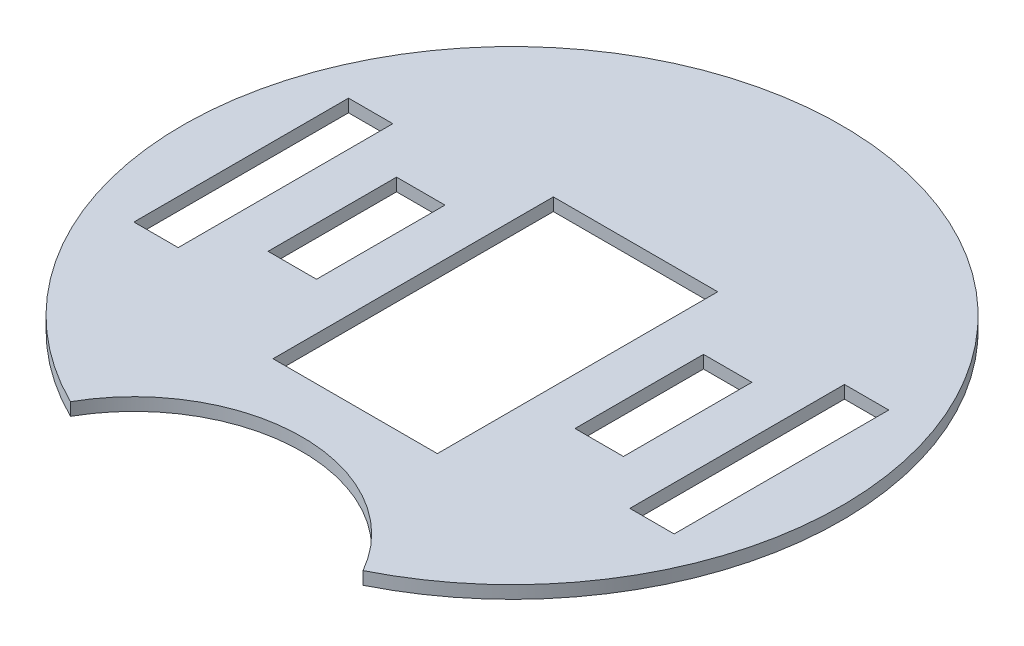
SolidWorks part; units mm, degrees
ref_plane "Front Plane" through (0, 0, 0) normal (0, 0, 1) x (1, 0, 0)
ref_plane "Top Plane" through (0, 0, 0) normal (0, 1, 0) x (1, 0, 0)
ref_plane "Right Plane" through (0, 0, 0) normal (1, 0, 0) x (0, 0, -1)
sketch "Sketch1" plane through (0, 0, 0) normal (0, 1, 0) x (1, 0, 0)
  line L0 (0, -86.0416) -> (-33.2911, -67.2064) construction
  line L1 (0, -86.0416) -> (0, 0) construction
  arc A0 (33.2911, -67.2064) -> (-33.2911, -67.2064) centre (0, 0) ccw
  arc A1 (33.2911, -67.2064) -> (-33.2911, -67.2064) centre (0, -86.0416) ccw
  dimension "D1" = 150
  dimension "D2" = 76.5
  dimension "D3" = 60.5
extrude "Boss-Extrude1" add sketch "Sketch1" along normal blind 2.9
sketch "solenoid placement" plane through (0, 2.9, 0) normal (0, 1, 0) x (1, 0, 0)
  line L4 (-18.7, -35.7) -> (18.7, -35.7)
  line L5 (18.7, -35.7) -> (18.7, 28.1)
  line L6 (18.7, 28.1) -> (-18.7, 28.1)
  line L7 (-18.7, 28.1) -> (-18.7, -35.7)
  line L8 (-18.7, -35.7) -> (18.7, -35.7)
  line L9 (18.7, -35.7) -> (18.7, 28.1)
  line L10 (18.7, 28.1) -> (-18.7, 28.1)
  line L11 (-18.7, 28.1) -> (-18.7, -35.7)
  circle A1 centre (0, 0) radius 75 construction
  arc A2 (33.2911, -67.2064) -> (-33.2911, -67.2064) centre (0, 0) ccw construction
  dimension "D1" = 0
extrude "Cut-Extrude1" cut sketch "solenoid placement" against normal through all
sketch "Sketch2" plane through (0, 2.9, 0) normal (0, 1, 0) x (1, 0, 0)
  line L0 (51.6937, -24.2881) -> (51.6937, 23.9564) construction
  line L1 (-61.1724, -24.2881) -> (-51.6937, -24.2881) construction
  line L2 (-61.1724, -24.2881) -> (-61.1724, 23.9564) construction
  line L3 (-61.1724, 23.9564) -> (-51.6937, 23.9564) construction
  line L4 (-51.6937, -24.2881) -> (-51.6937, 23.9564) construction
  line L5 (61.1724, 23.9564) -> (51.6937, 23.9564) construction
  line L6 (61.1724, -24.2881) -> (61.1724, 23.9564) construction
  line L7 (61.1724, -24.2881) -> (51.6937, -24.2881) construction
  line L8 (61.4724, -24.5881) -> (61.4724, 24.2564)
  line L9 (61.4724, -24.5881) -> (51.3937, -24.5881)
  line L10 (51.3937, -24.5881) -> (51.3937, 24.2564)
  line L11 (61.4724, 24.2564) -> (51.3937, 24.2564)
  line L12 (0, 0) -> (0, 75) construction
  line L13 (-61.4724, 24.2564) -> (-51.3937, 24.2564)
  line L14 (-51.3937, -24.5881) -> (-51.3937, 24.2564)
  line L15 (-61.4724, -24.5881) -> (-51.3937, -24.5881)
  line L16 (-61.4724, -24.5881) -> (-61.4724, 24.2564)
  arc A0 (33.2911, -67.2064) -> (-33.2911, -67.2064) centre (0, 0) ccw construction
extrude "Cut-Extrude2" cut sketch "Sketch2" against normal through all
sketch "Sketch3" plane through (0, 2.9, 0) normal (0, 1, 0) x (1, 0, 0)
  line L4 (-40.4368, -15.0893) -> (-29.4137, -15.0893)
  line L5 (-29.4137, -15.0893) -> (-29.4137, 14.1493)
  line L6 (-29.4137, 14.1493) -> (-40.4368, 14.1493)
  line L7 (-40.4368, 14.1493) -> (-40.4368, -15.0893)
  line L8 (-40.4368, -15.0893) -> (-29.4137, -15.0893)
  line L9 (-29.4137, -15.0893) -> (-29.4137, 14.1493)
  line L10 (-29.4137, 14.1493) -> (-40.4368, 14.1493)
  line L11 (-40.4368, 14.1493) -> (-40.4368, -15.0893)
  line L12 (40.4368, -15.0893) -> (40.4368, 14.1493)
  line L13 (40.4368, 14.1493) -> (29.4137, 14.1493)
  line L14 (29.4137, 14.1493) -> (29.4137, -15.0893)
  line L15 (29.4137, -15.0893) -> (40.4368, -15.0893)
  line L16 (40.4368, -15.0893) -> (40.4368, 14.1493)
  line L17 (40.4368, 14.1493) -> (29.4137, 14.1493)
  line L18 (29.4137, 14.1493) -> (29.4137, -15.0893)
  line L19 (29.4137, -15.0893) -> (40.4368, -15.0893)
  point P8 (0, 0)
  point P9 (0, 0)
  point P10 (0, 0)
  point P11 (0, 0)
  point P12 (0, 0)
  point P13 (0, 0)
  point P14 (0, 0)
  point P15 (0, 0)
  dimension "D1" = 0
  dimension "D2" = 0
extrude "Cut-Extrude3" cut sketch "Sketch3" against normal through all
equation "\"smallPulleyTeeth\"= 15"
equation "\"largePulleyTeeth\"= 30"
equation "\"eighthThick\"= 2.9mm"
equation "\"sixteenthThick\" = 1.7mm"
equation "\"wheelEighthThick\"=3.0mm"
equation "\"quarterThick\"=5.6mm"
equation "\"OD\" = 150mm"
equation "\"puckAngle\" = 60.5deg"
equation "\"D1@Sketch1\"=\"OD\""
equation "\"puckDiam\" = 76.5mm"
equation "\"D2@Sketch1\"=\"puckDiam\""
equation "\"D3@Sketch1\"=\"puckAngle\""
equation "\"D1@Boss-Extrude1\"=\"eighthThick\""
equation "\"axlePress\" = 5.8mm"
equation "\"press\" = 0.3mm"
equation "\"wheelClear\" = 0.3mm"
equation "\"D1@Sketch2\"=\"wheelClear\""
